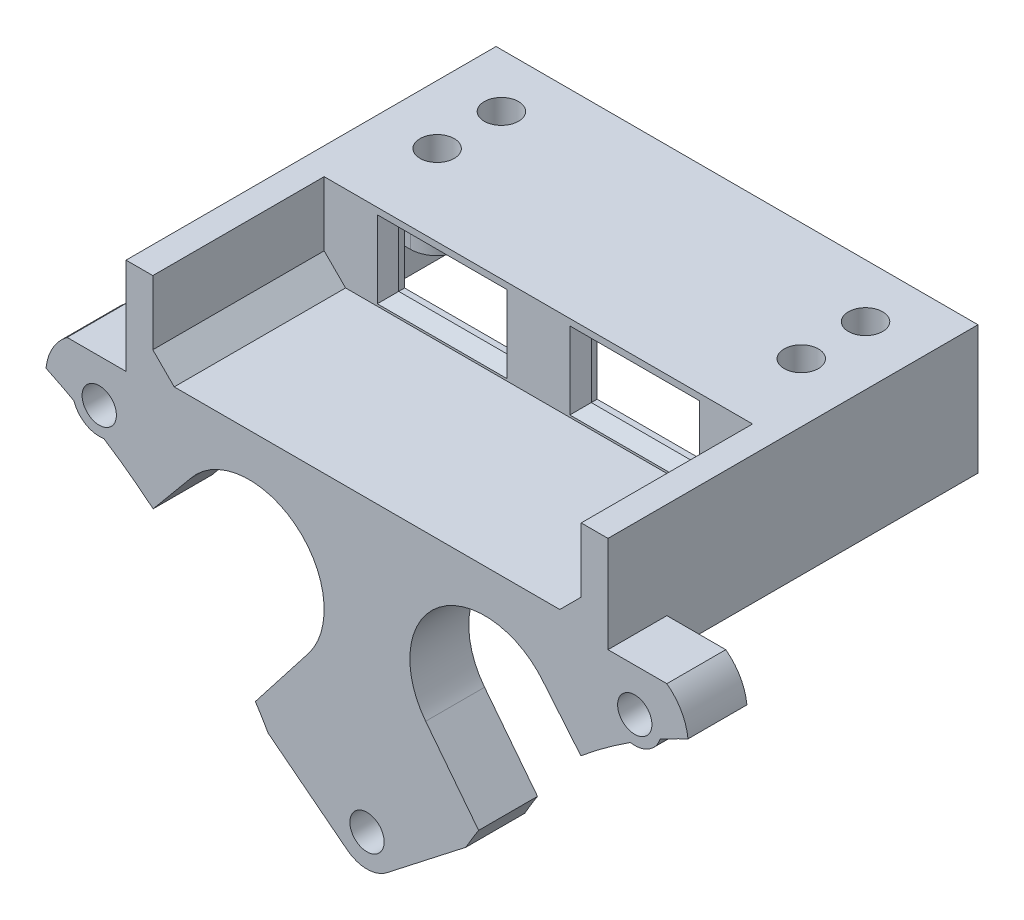
SolidWorks part; units mm, degrees
ref_plane "前视基准面" through (0, 0, 0) normal (0, 0, 1) x (1, 0, 0)
ref_plane "上视基准面" through (0, 0, 0) normal (0, 1, 0) x (1, 0, 0)
ref_plane "右视基准面" through (0, 0, 0) normal (1, 0, 0) x (0, 0, -1)
sketch "草图1" plane through (0, 0, 0) normal (0, 0, 1) x (1, 0, 0)
  line L0 (0, 0) -> (22.5, 0)
  line L1 (22.5, 0) -> (22.5, 12)
  line L2 (22.5, 12) -> (-22.5, 12)
  line L3 (-22.5, 12) -> (-22.5, 0)
  line L4 (-22.5, 0) -> (0, 0)
extrude "凸台-拉伸1" add sketch "草图1" along normal blind 34.55
sketch "草图2" plane through (0, 0, 34.55) normal (0, 0, 1) x (1, 0, 0)
  line L0 (-20, 12) -> (20, 12)
  line L1 (22.5, 12) -> (-22.5, 12) construction
  line L2 (20, 12) -> (20, 4)
  line L3 (20, 4) -> (-20, 4)
  line L4 (0, -6.6) -> (0, 6.6) construction
  line L5 (-20, 12) -> (-20, 4)
  point P9 (0, 4)
  point P10 (0, 12)
extrude "切除-拉伸1" cut sketch "草图2" against normal blind 16
sketch "草图3" plane through (0, 0, 0) normal (0, -1, 0) x (1, 0, 0)
  line L1 (0, 2) -> (20, 2)
  line L2 (20, 2) -> (20, 17)
  line L3 (20, 17) -> (-20, 17)
  line L4 (-20, 17) -> (-20, 2)
  line L5 (-20, 2) -> (0, 2)
extrude "切除-拉伸2" cut sketch "草图3" against normal blind 10
sketch "草图4" plane through (0, 0, 18.55) normal (0, 0, 1) x (1, 0, 0)
  line L0 (-14.04, 10.4) -> (-14.04, 5.2)
  line L1 (-13.94, 10.3) -> (-13.94, 5.3) construction
  line L7 (-13.94, 5.3) -> (-4.04, 5.3) construction
  line L8 (-13.94, 10.3) -> (-4.04, 10.3) construction
  line L9 (-4.04, 10.3) -> (-4.04, 5.3) construction
  line L10 (-14.04, 5.2) -> (-3.94, 5.2)
  line L11 (-3.94, 10.4) -> (-3.94, 5.2)
  line L12 (-14.04, 10.4) -> (-3.94, 10.4)
  line L13 (0, -6.6) -> (0, 6.6) construction
  line L14 (4.04, 10.3) -> (4.04, 5.3) construction
  line L15 (13.94, 10.3) -> (4.04, 10.3) construction
  line L16 (13.94, 5.3) -> (4.04, 5.3) construction
  line L17 (13.94, 10.3) -> (13.94, 5.3) construction
  line L18 (14.04, 10.4) -> (3.94, 10.4)
  line L19 (3.94, 10.4) -> (3.94, 5.2)
  line L20 (14.04, 5.2) -> (3.94, 5.2)
  line L21 (14.04, 10.4) -> (14.04, 5.2)
  dimension "D1" = 0.1
extrude "切除-拉伸3" cut sketch "草图4" against normal blind 10
chamfer "倒角1" distance 2 angle 45 2 edges at (20, 4, 26.55) (-20, 4, 26.55)
chamfer "倒角2" distance 1 angle 45 8 edges at (-8.99, 5.2, 18.55) (-14.04, 7.8, 18.55) (-8.99, 10.4, 18.55) (-3.94, 7.8, 18.55) (8.99, 10.4, 18.55) (3.94, 7.8, 18.55) (8.99, 5.2, 18.55) (14.04, 7.8, 18.55)
sketch "草图6" plane through (0, 12, 0) normal (0, 1, 0) x (1, 0, 0)
  line L0 (22.5, 0) -> (22.5, -13.5)
  line L2 (22.5, -34.55) -> (22.5, 0) construction
  line L3 (22.5, -13.5) -> (17, -13.5)
  line L4 (14.5, -11) -> (14.5, -5)
  line L5 (14.5, -5) -> (14.5, 0)
  line L6 (22.5, 0) -> (-22.5, 0) construction
  line L7 (14.5, 0) -> (22.5, 0)
  line L8 (0, -6.6) -> (0, 6.6) construction
  line L9 (-14.5, 0) -> (-22.5, 0)
  line L10 (-14.5, -5) -> (-14.5, 0)
  line L11 (-14.5, -11) -> (-14.5, -5)
  line L12 (-22.5, -13.5) -> (-17, -13.5)
  line L13 (-22.5, 0) -> (-22.5, -13.5)
  circle A0 centre (17, -5) radius 1.6
  circle A1 centre (17, -11) radius 1.6
  arc A2 (17, -13.5) -> (14.5, -11) centre (17, -11) cw
  arc A3 (-17, -13.5) -> (-14.5, -11) centre (-17, -11) ccw
  circle A4 centre (-17, -11) radius 1.6
  circle A5 centre (-17, -5) radius 1.6
extrude "凸台-拉伸2" add sketch "草图6" against normal blind 6.9
sketch "草图7" plane through (0, 12, 0) normal (0, 1, 0) x (1, 0, 0)
  circle A0 centre (17, -5) radius 1.6
  circle A1 centre (17, -11) radius 1.6
  circle A2 centre (-17, -5) radius 1.6
  circle A3 centre (-17, -11) radius 1.6
extrude "切除-拉伸4" cut sketch "草图7" against normal blind 10
sketch "草图8" plane through (0, 0, 34.55) normal (0, 0, 1) x (1, 0, 0)
  line L1 (1.843, -25.3671) -> (9.2306, -19.6151)
  line L2 (-18, 4) -> (18, 4) construction
  line L3 (0, -6.6) -> (0, 6.6) construction
  line L5 (16.5232, -2.6996) -> (19.968, -6.8465)
  line L6 (-1.843, -25.3671) -> (-9.2306, -19.6151)
  line L7 (-5.4768, -11.3004) -> (-10.4216, -17.6514)
  line L8 (5.4768, -11.3004) -> (10.4216, -17.6514)
  line L9 (-16.5232, -2.6996) -> (-19.968, -6.8465)
  line L10 (22.5, 3) -> (22.5, 4)
  line L11 (-22.5, 12) -> (-22.5, 0) construction
  line L12 (-22.5, 3) -> (-28, 3)
  line L13 (-22.5, 3) -> (-22.5, 4)
  line L14 (22.5, 3) -> (28, 3)
  line L15 (-22.5, 4) -> (22.5, 4)
  circle A1 centre (25, -1) radius 1.6
  circle A3 centre (0, -23) radius 1.6
  arc A4 (-1.843, -25.3671) -> (1.843, -25.3671) centre (0, -23) ccw
  circle A6 centre (-25, -1) radius 1.6
  arc A8 (29.9729, -0.4804) -> (27.3654, -1.8093) centre (50, -43) ccw
  arc A9 (10.4216, -17.6514) -> (9.2306, -19.6151) centre (50, -43) ccw
  arc A10 (16.5232, -2.6996) -> (5.4768, -11.3004) centre (11, -7) ccw
  arc A11 (24.5837, -3.4651) -> (27.3654, -1.8093) centre (25, -1) ccw
  arc A12 (24.5837, -3.4651) -> (19.968, -6.8465) centre (50, -43) ccw
  arc A13 (-10.4216, -17.6514) -> (-9.2306, -19.6151) centre (-50, -43) cw
  arc A14 (-16.5232, -2.6996) -> (-5.4768, -11.3004) centre (-11, -7) cw
  arc A15 (-24.5837, -3.4651) -> (-19.968, -6.8465) centre (-50, -43) cw
  arc A16 (-24.5837, -3.4651) -> (-27.3654, -1.8093) centre (-25, -1) cw
  arc A17 (-29.9729, -0.4804) -> (-27.3654, -1.8093) centre (-50, -43) cw
  arc A18 (-29.9729, -0.4804) -> (-28, 3) centre (-25, -1) cw
  arc A19 (29.9729, -0.4804) -> (28, 3) centre (25, -1) ccw
  point P23 (0, 4)
extrude "凸台-拉伸3" add sketch "草图8" against normal blind 5.5
sketch "草图10" plane through (0, 0, 0) normal (0, 0, -1) x (-1, 0, 0)
  line L1 (22.5, 0) -> (-22.5, 0) construction
  line L2 (-20, 0) -> (-20, 10)
  line L3 (-20, 10) -> (20, 10)
  line L4 (20, 10) -> (20, 0)
  line L5 (20, 0) -> (-20, 0)
extrude "切除-拉伸5" cut sketch "草图10" against normal blind 2
